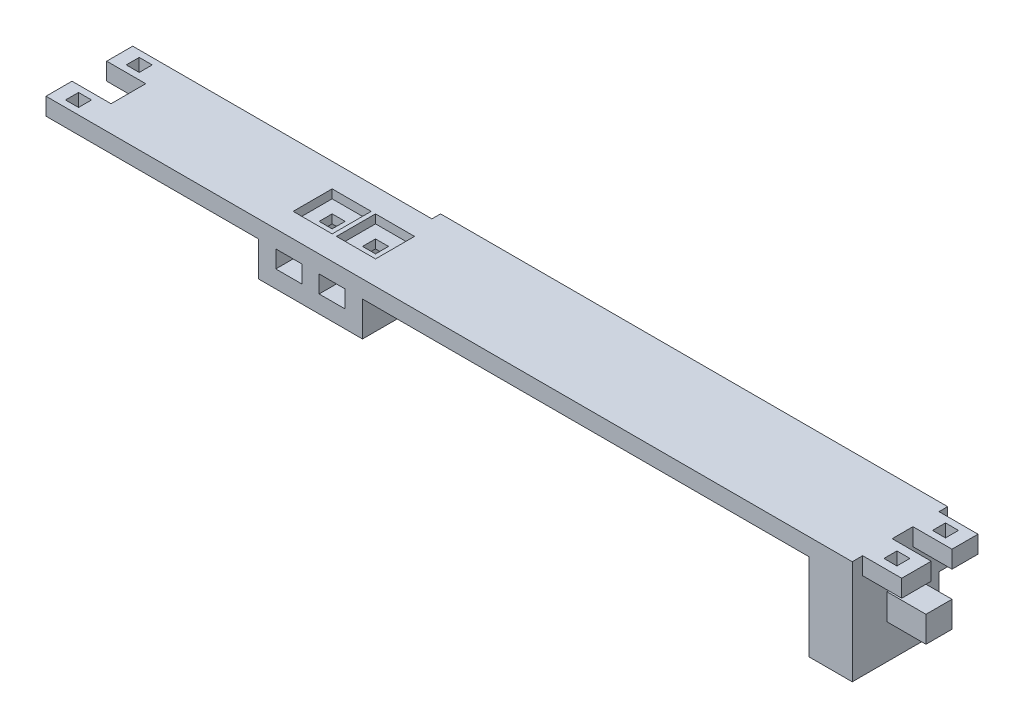
SolidWorks part; units mm, degrees
ref_plane "Front Plane" through (0, 0, 0) normal (0, 0, 1) x (1, 0, 0)
ref_plane "Top Plane" through (0, 0, 0) normal (0, 1, 0) x (1, 0, 0)
ref_plane "Right Plane" through (0, 0, 0) normal (1, 0, 0) x (0, 0, -1)
sketch "Sketch2" plane through (0, 0, 0) normal (0, 1, 0) x (1, 0, 0)
  line L1 (0, 0) -> (194.96, 0)
  line L2 (0, 0) -> (0, 6)
  line L3 (0, 6) -> (194.96, 6)
  line L4 (194.96, 0) -> (194.96, 6)
  dimension "D1" = 194.96
  dimension "D2" = 6
extrude "Boss-Extrude1" add sketch "Sketch2" along normal blind 4
sketch "Sketch3" plane through (0, 0, 0) normal (0, 0, -1) x (-1, 0, 0)
  line L0 (-194.96, 4) -> (0, 4) construction
  line L1 (-9, 4) -> (-185.96, 4)
  line L2 (-9, 4) -> (-9, 0)
  line L3 (-9, 0) -> (-185.96, 0)
  line L4 (-185.96, 4) -> (-185.96, 0)
  line L5 (-194.96, 0) -> (0, 0) construction
  line L7 (-194.96, 4) -> (-194.96, 0) construction
  line L8 (0, 4) -> (0, 0) construction
  dimension "D1" = 9
  dimension "D2" = 9
extrude "Boss-Extrude2" add sketch "Sketch3" against normal blind 14
sketch "Sketch4" plane through (9, 0, 0) normal (-1, 0, 0) x (0, 0, 1)
  line L0 (14, 0) -> (0, 0) construction
  line L1 (14, 4) -> (8, 4)
  line L2 (14, 4) -> (14, 0)
  line L3 (14, 0) -> (8, 0)
  line L4 (8, 4) -> (8, 0)
  line L6 (0, 0) -> (0, 4) construction
  dimension "D1" = 6
extrude "Boss-Extrude3" add sketch "Sketch4" along normal blind 9
sketch "Sketch5" plane through (185.96, 0, 0) normal (1, 0, 0) x (0, 0, -1)
  line L0 (-14, 4) -> (0, 4) construction
  line L1 (-11.6, 4) -> (-4.8, 4)
  line L2 (-11.6, 4) -> (-11.6, 0)
  line L3 (-11.6, 0) -> (-4.8, 0)
  line L4 (-4.8, 4) -> (-4.8, 0)
  line L5 (-14, 0) -> (0, 0) construction
  line L6 (-14, 4) -> (-14, 0) construction
  line L7 (0, 4) -> (0, 0) construction
  dimension "D1" = 2.4
  dimension "D2" = 4.8
extrude "Boss-Extrude4" add sketch "Sketch5" along normal blind 9
sketch "Sketch6" plane through (0, 4, 0) normal (0, 1, 0) x (1, 0, 0)
  line L0 (0, 6) -> (0, 0) construction
  line L1 (3, 4.5) -> (6, 4.5)
  line L2 (3, 4.5) -> (3, 1.5)
  line L3 (3, 1.5) -> (6, 1.5)
  line L4 (6, 4.5) -> (6, 1.5)
  line L5 (194.96, 6) -> (0, 6) construction
  line L7 (0, -14) -> (185.96, -14) construction
  line L8 (3, -9.5) -> (6, -9.5)
  line L9 (3, -9.5) -> (3, -12.5)
  line L10 (3, -12.5) -> (6, -12.5)
  line L11 (6, -9.5) -> (6, -12.5)
  line L12 (0, -14) -> (0, -8) construction
  line L13 (194.96, 0) -> (194.96, 6) construction
  line L14 (188.96, 4.5) -> (191.96, 4.5)
  line L15 (188.96, 4.5) -> (188.96, 1.5)
  line L16 (188.96, 1.5) -> (191.96, 1.5)
  line L17 (191.96, 4.5) -> (191.96, 1.5)
  line L18 (194.96, -4.8) -> (194.96, -11.6) construction
  line L19 (191.96, -6.7) -> (188.96, -6.7)
  line L20 (191.96, -6.7) -> (191.96, -9.7)
  line L21 (191.96, -9.7) -> (188.96, -9.7)
  line L22 (188.96, -6.7) -> (188.96, -9.7)
  line L23 (194.96, -4.8) -> (185.96, -4.8) construction
  dimension "D1" = 3
  dimension "D2" = 3
  dimension "D3" = 3
  dimension "D4" = 1.5
  dimension "D5" = 3
  dimension "D6" = 1.5
  dimension "D7" = 3
  dimension "D8" = 1.5
  dimension "D9" = 3
  dimension "D10" = 3
  dimension "D11" = 3
  dimension "D12" = 3
  dimension "D13" = 3
  dimension "D14" = 3
  dimension "D15" = 1.9
extrude "Cut-Extrude1" cut sketch "Sketch6" against normal up to next
sketch "Sketch7" plane through (0, 0, 0) normal (0, -1, 0) x (1, 0, 0)
  line L0 (194.96, -6) -> (0, -6) construction
  line L1 (185.96, 14) -> (175.96, 14)
  line L2 (185.96, 14) -> (185.96, -6)
  line L3 (185.96, -6) -> (175.96, -6)
  line L4 (175.96, 14) -> (175.96, -6)
  dimension "D1" = 10
extrude "Boss-Extrude5" add sketch "Sketch7" along normal blind 20
sketch "Sketch8" plane through (0, 0, 0) normal (0, -1, 0) x (1, 0, 0)
  line L0 (175.96, -6) -> (0, -6) construction
  line L1 (49, -6) -> (185.96, -6)
  line L2 (49, -6) -> (49, 0)
  line L3 (49, 0) -> (185.96, 0)
  line L4 (185.96, -6) -> (185.96, 0)
  line L5 (185.96, -6) -> (185.96, 14) construction
  line L6 (9, 8) -> (9, 0) construction
  dimension "D1" = 40
  dimension "D2" = 6
extrude "Boss-Extrude6" add sketch "Sketch8" along normal blind 8
chamfer "Chamfer1" distance 12 angle 50 1 edges at (175.96, -8, -3) first distance on face at (175.96, -9.3333, 2.6667)
sketch "Sketch9" plane through (0, 0, 0) normal (0, 0, 1) x (1, 0, 0)
  line L0 (175.96, 0) -> (0, 0) construction
  line L1 (49, -8) -> (55, -8)
  line L2 (49, -8) -> (49, 0)
  line L3 (49, 0) -> (55, 0)
  line L5 (161.659, -8) -> (49, -8) construction
  line L6 (61, -8) -> (73, -8)
  line L8 (61, 0) -> (73, 0)
  line L9 (73, -8) -> (73, 0)
  line L10 (175.96, 0) -> (49, 0) construction
  line L11 (55, 0) -> (61, 0)
  line L12 (55, -8) -> (61, -8)
  dimension "D1" = 24
extrude "Boss-Extrude7" add sketch "Sketch9" along normal up to surface (14 mm away) up to face at (120.64, -5.3333, 14)
sketch "Sketch10" plane through (0, 0, 14) normal (0, 0, 1) x (1, 0, 0)
  line L0 (49, 0) -> (0, 0) construction
  line L1 (53, 0) -> (59, 0)
  line L2 (53, 0) -> (53, -4)
  line L3 (53, -4) -> (59, -4)
  line L4 (59, 0) -> (59, -4)
  line L5 (49, 0) -> (49, -8) construction
  line L6 (0, 4) -> (185.96, 4) construction
  line L7 (63, 0) -> (69, 0)
  line L8 (63, 0) -> (63, -4)
  line L9 (63, -4) -> (69, -4)
  line L10 (69, 0) -> (69, -4)
  dimension "D1" = 6
  dimension "D2" = 4
  dimension "D3" = 0
  dimension "D4" = 4
  dimension "D5" = 6
  dimension "D6" = 4
extrude "Cut-Extrude2" cut sketch "Sketch10" against normal up to next
sketch "Sketch11" plane through (0, 4, 0) normal (0, 1, 0) x (1, 0, 0)
  line L0 (53, 6) -> (53, -14) construction
  line L1 (54.5, -2.5) -> (57.5, -2.5)
  line L2 (54.5, -2.5) -> (54.5, -5.5)
  line L3 (54.5, -5.5) -> (57.5, -5.5)
  line L4 (57.5, -2.5) -> (57.5, -5.5)
  line L5 (0, -14) -> (185.96, -14) construction
  line L8 (63, 6) -> (63, -14) construction
  line L9 (64.5, -5.5) -> (67.5, -5.5)
  line L10 (64.5, -5.5) -> (64.5, -2.5)
  line L11 (64.5, -2.5) -> (67.5, -2.5)
  line L12 (67.5, -5.5) -> (67.5, -2.5)
  dimension "D1" = 1.5
  dimension "D2" = 3
  dimension "D3" = 3
  dimension "D4" = 8.5
  dimension "D5" = 3
  dimension "D6" = 3
  dimension "D7" = 1.5
  dimension "D8" = 8.5
extrude "Cut-Extrude3" cut sketch "Sketch11" against normal up to next
sketch "Sketch12" plane through (0, 0, -6) normal (0, 0, -1) x (-1, 0, 0)
  line L0 (-194.96, 4) -> (0, 4) construction
  line L1 (-185.96, 4) -> (-69, 4)
  line L2 (-185.96, 4) -> (-185.96, -8)
  line L3 (-185.96, -8) -> (-69, -8)
  line L4 (-69, 4) -> (-69, -8)
  line L5 (-49, -8) -> (-161.659, -8) construction
  line L6 (-185.96, -20) -> (-185.96, 0) construction
  line L7 (-69, 0) -> (-69, -4) construction
  dimension "D1" = 0
  dimension "D2" = 0
extrude "Boss-Extrude8" add sketch "Sketch12" along normal blind 2
sketch "Sketch13" plane through (185.96, 0, 0) normal (1, 0, 0) x (0, 0, -1)
  line L0 (-4.8, 0) -> (-11.6, 0) construction
  line L1 (-6, -6) -> (0, -6)
  line L2 (-6, -6) -> (-6, -12)
  line L3 (-6, -12) -> (0, -12)
  line L4 (0, -6) -> (0, -12)
  line L5 (-14, 4) -> (-14, -20) construction
  line L8 (-11.6, 4) -> (-11.6, 0) construction
  line L9 (6, 4) -> (6, 0) construction
  line L10 (-11.6, 4) -> (-11.6, 0) construction
  dimension "D1" = 6
  dimension "D2" = 6
  dimension "D3" = 6
  dimension "D4" = 8
extrude "Boss-Extrude9" add sketch "Sketch13" along normal blind 9
sketch "Sketch14" plane through (0, 4, 0) normal (0, 1, 0) x (1, 0, 0)
  line L0 (64.5, -2.5) -> (64.5, -5.5) construction
  line L1 (61.5, 0.5) -> (70.5, 0.5)
  line L2 (61.5, 0.5) -> (61.5, -8.5)
  line L3 (61.5, -8.5) -> (70.5, -8.5)
  line L4 (70.5, 0.5) -> (70.5, -8.5)
  line L5 (67.5, -2.5) -> (64.5, -2.5) construction
  line L6 (67.5, -5.5) -> (67.5, -2.5) construction
  line L7 (64.5, -5.5) -> (67.5, -5.5) construction
  line L8 (57.5, -5.5) -> (57.5, -2.5) construction
  line L9 (51.5, 0.5) -> (60.5, 0.5)
  line L10 (51.5, 0.5) -> (51.5, -8.5)
  line L11 (51.5, -8.5) -> (60.5, -8.5)
  line L12 (60.5, 0.5) -> (60.5, -8.5)
  line L13 (54.5, -2.5) -> (54.5, -5.5) construction
  line L14 (54.5, -5.5) -> (57.5, -5.5) construction
  dimension "D1" = 3
  dimension "D2" = 3
  dimension "D3" = 3
  dimension "D4" = 3
  dimension "D5" = 3
  dimension "D6" = 3
  dimension "D7" = 3
extrude "Cut-Extrude4" cut sketch "Sketch14" against normal blind 2
